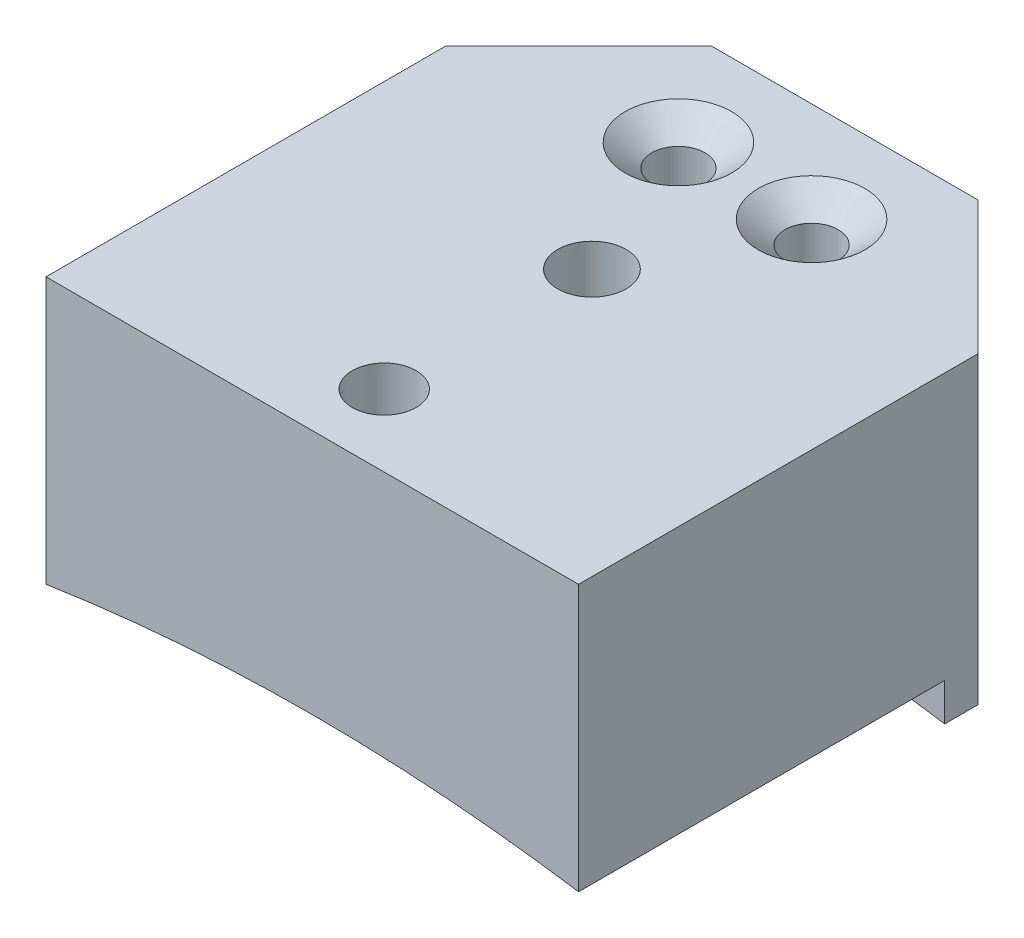
SolidWorks part; units mm, degrees
ref_plane "Front Plane" through (0, 0, 0) normal (0, 0, 1) x (1, 0, 0)
ref_plane "Top Plane" through (0, 0, 0) normal (0, 1, 0) x (1, 0, 0)
ref_plane "Right Plane" through (0, 0, 0) normal (1, 0, 0) x (0, 0, -1)
sketch "Sketch1" plane through (0, 0, 0) normal (0, 1, 0) x (1, 0, 0)
  line L0 (-28.5118, 6.4953) -> (-22.1618, 12.8453)
  line L1 (-22.1618, 12.8453) -> (-9.4618, 12.8453)
  line L2 (-28.5118, 6.4953) -> (-28.5118, -12.5547)
  line L3 (-28.5118, -12.5547) -> (-3.1118, -12.5547)
  line L4 (-3.1118, 6.4953) -> (-3.1118, -12.5547)
  line L5 (-9.4618, 12.8453) -> (-3.1118, 6.4953)
  line L6 (-15.8118, -12.5547) -> (-15.8118, 12.8453) construction
  line L8 (-3.1118, 6.4953) -> (-3.1118, 12.8453) construction
  line L9 (-3.1118, 12.8453) -> (-9.4618, 12.8453) construction
  dimension "D1" = 12.7
  dimension "D2" = 25.4
  dimension "D3" = 25.4
extrude "Boss-Extrude1" add sketch "Sketch1" along normal blind 12.7
sketch "Sketch2" plane through (0, 0, 12.5547) normal (0, 0, 1) x (1, 0, 0)
  circle A0 centre (-15.8118, -82.8523) radius 83.82
  dimension "D1" = 167.64
extrude "Cut-Extrude1" cut sketch "Sketch2" against normal through all both and the other way through all
sketch "Sketch5" plane through (0, 0, -12.8453) normal (0, 0, -1) x (-1, 0, 0)
  line L0 (3.1118, 12.7) -> (3.1118, 0) construction
  line L1 (3.1118, 12.7) -> (3.1118, 0)
  line L4 (28.5118, 12.7) -> (28.5118, 0) construction
  line L5 (28.5118, 12.7) -> (28.5118, 0)
  line L6 (28.5118, -1.7992) -> (28.5118, 0)
  line L7 (3.1118, -1.7992) -> (3.1118, 0)
  line L8 (3.1118, 12.7) -> (28.5118, 12.7)
  arc A0 (3.1118, -1.7992) -> (28.5118, -1.7992) centre (15.8118, -82.8523) cw
  arc A1 (28.5118, 0) -> (3.1118, 0) centre (15.8118, -82.8523) ccw construction
  arc A2 (28.5118, 0) -> (3.1118, 0) centre (15.8118, -82.8523) ccw construction
  dimension "D1" = 82.042
extrude "Boss-Extrude2" add sketch "Sketch5" against normal blind 7.9375
chamfer "Chamfer1" distance 6.35 angle 45 2 edges at (-28.5118, 5.4504, -12.8453) (-3.1118, 5.4504, -12.8453)
hole_wizard "CSK for #10 Flat Head Machine Screw (100)1" positions "Sketch3" profile "Sketch4" countersink size "#10" standard "ANSI Inch" end condition through all
sketch "Sketch3" plane through (0, 12.7, 0) normal (0, 1, 0) x (1, 0, 0)
  line L0 (-15.8118, 12.8453) -> (-15.8118, 3.4006) construction
  line L1 (-9.4618, 12.8453) -> (-22.1618, 12.8453) construction
  point P0 (-18.9868, 8.0828)
  point P12 (-12.6368, 8.0828)
  dimension "D1" = 4.7625
  dimension "D2" = 3.175
sketch "Sketch4" plane through (-18.9868, 12.7, -8.0828) normal (1, 0, 0) x (0, 0, 1)
  line L0 (0, 0) -> (0, 14.4992)
  line L1 (0, 14.4992) -> (1.27, 14.4992)
  line L2 (1.27, 14.4992) -> (1.27, 1.0657)
  line L3 (1.27, 1.0657) -> (2.54, 0)
  line L5 (2.54, 0) -> (0, 0)
  line L6 (-1.27, 1.0657) -> (-2.54, 0) construction
  line L11 (0, -6.35) -> (0, 107.95) construction
  dimension "Thru Hole Dia." = 2.54
  dimension "Thru Hole Depth" = 14.4992
  dimension "Near C'Sink Dia." = 5.08
  dimension "Near C'Sink Angle" = 100
sketch "Sketch6" plane through (0, 12.7, 0) normal (0, 1, 0) x (1, 0, 0)
  spline S0 degree 3 poles (-15.9109, -10.6497) (-15.6088, -10.6497) (-15.4088, -10.6093) (-15.0421, -10.4569) (-14.8723, -10.3433) (-14.6614, -10.1321) (-14.5971, -10.0536) (-14.4867, -9.888) (-14.44, -9.8004) (-14.3254, -9.523) (-14.286, -9.3252) (-14.2863, -9.0237) (-14.2962, -8.9248) (-14.3351, -8.7299) (-14.3646, -8.633) (-14.4412, -8.4488) (-14.488, -8.3613) (-14.5989, -8.1955) (-14.6633, -8.1172) (-14.8743, -7.9067) (-15.0444, -7.7932) (-15.4113, -7.6415) (-15.6118, -7.6017) (-15.9102, -7.6018) (-16.0112, -7.6118) (-16.2064, -7.6508) (-16.3014, -7.6796) (-16.5784, -7.7944) (-16.7462, -7.9063) (-16.9595, -8.1198) (-17.0224, -8.1968) (-17.1327, -8.362) (-17.1804, -8.4512) (-17.2567, -8.6357) (-17.2855, -8.7307) (-17.3244, -8.9262) (-17.3342, -9.0271) (-17.3341, -9.3253) (-17.2941, -9.5259) (-17.142, -9.8926) (-17.0285, -10.0627) (-16.8176, -10.2736) (-16.7392, -10.3379) (-16.5735, -10.4485) (-16.486, -10.4953) (-16.3014, -10.5718) (-16.2047, -10.6011) (-16.0099, -10.6398) (-15.9109, -10.6497) (-15.6088, -10.6497) (-15.4088, -10.6093) knots -0.03125 -0.03125 0 0 0.0625 0.0625 0.125 0.125 0.15625 0.15625 0.1875 0.1875 0.25 0.25 0.28125 0.28125 0.3125 0.3125 0.34375 0.34375 0.375 0.375 0.4375 0.4375 0.5 0.5 0.53125 0.53125 0.5625 0.5625 0.625 0.625 0.65625 0.65625 0.6875 0.6875 0.71875 0.71875 0.75 0.75 0.8125 0.8125 0.875 0.875 0.90625 0.90625 0.9375 0.9375 0.96875 0.96875 1 1 1.0625 1.0625 1.125 only from (-15.8102, -10.6497) to (-15.8102, -10.6497) construction
  spline S1 degree 3 poles (-15.9109, -10.6497) (-15.6088, -10.6497) (-15.4088, -10.6093) (-15.0421, -10.4569) (-14.8723, -10.3433) (-14.6614, -10.1321) (-14.5971, -10.0536) (-14.4867, -9.888) (-14.44, -9.8004) (-14.3254, -9.523) (-14.286, -9.3252) (-14.2863, -9.0237) (-14.2962, -8.9248) (-14.3351, -8.7299) (-14.3646, -8.633) (-14.4412, -8.4488) (-14.488, -8.3613) (-14.5989, -8.1955) (-14.6633, -8.1172) (-14.8743, -7.9067) (-15.0444, -7.7932) (-15.4113, -7.6415) (-15.6118, -7.6017) (-15.9102, -7.6018) (-16.0112, -7.6118) (-16.2064, -7.6508) (-16.3014, -7.6796) (-16.5784, -7.7944) (-16.7462, -7.9063) (-16.9595, -8.1198) (-17.0224, -8.1968) (-17.1327, -8.362) (-17.1804, -8.4512) (-17.2567, -8.6357) (-17.2855, -8.7307) (-17.3244, -8.9262) (-17.3342, -9.0271) (-17.3341, -9.3253) (-17.2941, -9.5259) (-17.142, -9.8926) (-17.0285, -10.0627) (-16.8176, -10.2736) (-16.7392, -10.3379) (-16.5735, -10.4485) (-16.486, -10.4953) (-16.3014, -10.5718) (-16.2047, -10.6011) (-16.0099, -10.6398) (-15.9109, -10.6497) (-15.6088, -10.6497) (-15.4088, -10.6093) knots -0.03125 -0.03125 0 0 0.0625 0.0625 0.125 0.125 0.15625 0.15625 0.1875 0.1875 0.25 0.25 0.28125 0.28125 0.3125 0.3125 0.34375 0.34375 0.375 0.375 0.4375 0.4375 0.5 0.5 0.53125 0.53125 0.5625 0.5625 0.625 0.625 0.65625 0.65625 0.6875 0.6875 0.71875 0.71875 0.75 0.75 0.8125 0.8125 0.875 0.875 0.90625 0.90625 0.9375 0.9375 0.96875 0.96875 1 1 1.0625 1.0625 1.125 only from (-15.8102, -10.6497) to (-15.8102, -10.6497)
  spline S2 degree 3 poles (-17.442, 0.8881) (-17.442, 0.5646) (-17.3987, 0.3504) (-17.2355, -0.0422) (-17.1139, -0.2241) (-16.8877, -0.4499) (-16.8036, -0.5187) (-16.6263, -0.6369) (-16.5325, -0.687) (-16.2355, -0.8097) (-16.0236, -0.8519) (-15.7008, -0.8516) (-15.5949, -0.8409) (-15.3862, -0.7993) (-15.2825, -0.7677) (-15.0851, -0.6857) (-14.9915, -0.6355) (-14.814, -0.5168) (-14.7301, -0.4479) (-14.5047, -0.222) (-14.3832, -0.0397) (-14.2207, 0.3532) (-14.178, 0.5678) (-14.1782, 0.8874) (-14.1889, 0.9955) (-14.2306, 1.2046) (-14.2615, 1.3063) (-14.3435, 1.5041) (-14.3946, 1.5994) (-14.5128, 1.7761) (-14.5805, 1.8587) (-14.7329, 2.0109) (-14.8153, 2.0784) (-14.9922, 2.1965) (-15.0878, 2.2476) (-15.2854, 2.3293) (-15.3871, 2.3601) (-15.5964, 2.4017) (-15.7045, 2.4123) (-16.0238, 2.4121) (-16.2385, 2.3692) (-16.6313, 2.2065) (-16.8134, 2.0849) (-17.0392, 1.8591) (-17.1081, 1.7751) (-17.2266, 1.5977) (-17.2767, 1.5039) (-17.3586, 1.3063) (-17.39, 1.2027) (-17.4314, 0.9941) (-17.442, 0.8881) (-17.442, 0.5646) (-17.3987, 0.3504) knots -0.03125 -0.03125 0 0 0.0625 0.0625 0.125 0.125 0.15625 0.15625 0.1875 0.1875 0.25 0.25 0.28125 0.28125 0.3125 0.3125 0.34375 0.34375 0.375 0.375 0.4375 0.4375 0.5 0.5 0.53125 0.53125 0.5625 0.5625 0.59375 0.59375 0.625 0.625 0.65625 0.65625 0.6875 0.6875 0.71875 0.71875 0.75 0.75 0.8125 0.8125 0.875 0.875 0.90625 0.90625 0.9375 0.9375 0.96875 0.96875 1 1 1.0625 1.0625 1.125 only from (-17.442, 0.7803) to (-17.442, 0.7803) construction
  spline S3 degree 3 poles (-17.442, 0.8881) (-17.442, 0.5646) (-17.3987, 0.3504) (-17.2355, -0.0422) (-17.1139, -0.2241) (-16.8877, -0.4499) (-16.8036, -0.5187) (-16.6263, -0.6369) (-16.5325, -0.687) (-16.2355, -0.8097) (-16.0236, -0.8519) (-15.7008, -0.8516) (-15.5949, -0.8409) (-15.3862, -0.7993) (-15.2825, -0.7677) (-15.0851, -0.6857) (-14.9915, -0.6355) (-14.814, -0.5168) (-14.7301, -0.4479) (-14.5047, -0.222) (-14.3832, -0.0397) (-14.2207, 0.3532) (-14.178, 0.5678) (-14.1782, 0.8874) (-14.1889, 0.9955) (-14.2306, 1.2046) (-14.2615, 1.3063) (-14.3435, 1.5041) (-14.3946, 1.5994) (-14.5128, 1.7761) (-14.5805, 1.8587) (-14.7329, 2.0109) (-14.8153, 2.0784) (-14.9922, 2.1965) (-15.0878, 2.2476) (-15.2854, 2.3293) (-15.3871, 2.3601) (-15.5964, 2.4017) (-15.7045, 2.4123) (-16.0238, 2.4121) (-16.2385, 2.3692) (-16.6313, 2.2065) (-16.8134, 2.0849) (-17.0392, 1.8591) (-17.1081, 1.7751) (-17.2266, 1.5977) (-17.2767, 1.5039) (-17.3586, 1.3063) (-17.39, 1.2027) (-17.4314, 0.9941) (-17.442, 0.8881) (-17.442, 0.5646) (-17.3987, 0.3504) knots -0.03125 -0.03125 0 0 0.0625 0.0625 0.125 0.125 0.15625 0.15625 0.1875 0.1875 0.25 0.25 0.28125 0.28125 0.3125 0.3125 0.34375 0.34375 0.375 0.375 0.4375 0.4375 0.5 0.5 0.53125 0.53125 0.5625 0.5625 0.59375 0.59375 0.625 0.625 0.65625 0.65625 0.6875 0.6875 0.71875 0.71875 0.75 0.75 0.8125 0.8125 0.875 0.875 0.90625 0.90625 0.9375 0.9375 0.96875 0.96875 1 1 1.0625 1.0625 1.125 only from (-17.442, 0.7803) to (-17.442, 0.7803)
extrude "Cut-Extrude2" cut sketch "Sketch6" against normal through all
